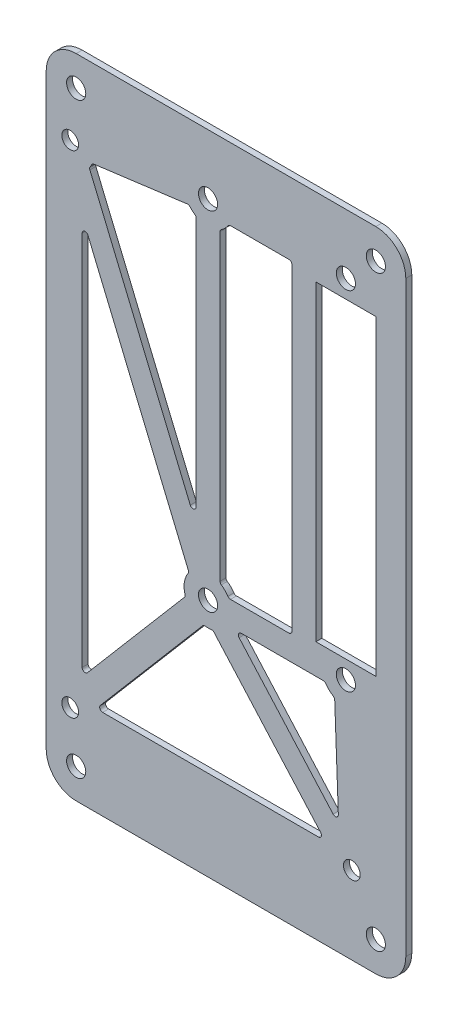
SolidWorks part; units mm, degrees
ref_plane "正面" through (0, 0, 0) normal (0, 0, 1) x (1, 0, 0)
ref_plane "平面" through (0, 0, 0) normal (0, 1, 0) x (1, 0, 0)
ref_plane "右側面" through (0, 0, 0) normal (1, 0, 0) x (0, 0, -1)
sketch "ｽｹｯﾁ1" plane through (0, 0, 0) normal (0, 0, 1) x (1, 0, 0)
  line L1 (-30, 54) -> (30, 54)
  line L2 (-30, 54) -> (-30, -54)
  line L3 (-30, -54) -> (30, -54)
  line L4 (30, 54) -> (30, -54)
  line L5 (-30, 54) -> (30, -54) construction
  line L6 (-30, -54) -> (30, 54) construction
  point P0 (0, 0)
  dimension "D1" = 108
  dimension "D2" = 60
extrude "ﾎﾞｽ - 押し出し1" add sketch "ｽｹｯﾁ1" along normal blind 1
sketch "ｽｹｯﾁ2" plane through (0, 0, 1) normal (0, 0, 1) x (1, 0, 0)
  line L0 (30, -54) -> (30, 54) construction
  line L1 (-3, 44) -> (20, 44) construction
  line L2 (-3, 44) -> (-3, -14) construction
  line L3 (-3, -14) -> (20, -14) construction
  line L4 (20, 44) -> (20, -14) construction
  line L5 (30, 54) -> (-30, 54) construction
  circle A0 centre (-3, 44) radius 1.6
  circle A1 centre (20, 44) radius 1.6
  circle A2 centre (-3, -14) radius 1.6
  circle A3 centre (20, -14) radius 1.6
  dimension "D5" = 3.2
  dimension "D6" = 3.2
  dimension "D7" = 3.2
  dimension "D8" = 3.2
  dimension "D1" = 58
  dimension "D2" = 23
  dimension "D3" = 10
  dimension "D4" = 10
extrude "ｶｯﾄ - 押し出し1" cut sketch "ｽｹｯﾁ2" against normal blind 5
sketch "ｽｹｯﾁ4" plane through (0, 0, 1) normal (0, 0, 1) x (1, 0, 0)
  line L0 (30, -54) -> (30, 54) construction
  line L1 (-25, -49) -> (25, -49) construction
  line L2 (-25, -49) -> (-25, 49) construction
  line L3 (-25, 49) -> (25, 49) construction
  line L4 (25, -49) -> (25, 49) construction
  line L5 (-25, -49) -> (25, 49) construction
  line L6 (-25, 49) -> (25, -49) construction
  line L8 (30, 54) -> (-30, 54) construction
  circle A0 centre (-25, 49) radius 1.6
  circle A1 centre (25, 49) radius 1.6
  circle A2 centre (-25, -49) radius 1.6
  circle A3 centre (25, -49) radius 1.6
  point P0 (0, 0)
  dimension "D3" = 3.2
  dimension "D4" = 3.2
  dimension "D5" = 3.2
  dimension "D6" = 3.2
  dimension "D1" = 5
  dimension "D2" = 5
extrude "ｶｯﾄ - 押し出し3" cut sketch "ｽｹｯﾁ4" against normal blind 5
fillet "ﾌｨﾚｯﾄ1" radius 5 4 edges at (30, -54, 0.5) (-30, -54, 0.5) (-30, 54, 0.5) (30, 54, 0.5)
sketch "ｽｹｯﾁ5" plane through (0, 0, 0) normal (0, 0, -1) x (-1, 0, 0)
  line L1 (-25, -11) -> (-15, -11)
  line L2 (-25, -11) -> (-25, 41)
  line L3 (-25, 41) -> (-15, 41)
  line L4 (-15, -11) -> (-15, 41)
  line L5 (-25, -11) -> (-15, 41) construction
  line L6 (-25, 41) -> (-15, -11) construction
  circle A0 centre (-20, 44) radius 1.6 construction
  circle A1 centre (-20, -14) radius 1.6 construction
  point P0 (-20, 15)
  dimension "D1" = 3
  dimension "D2" = 3
  dimension "D3" = 5
  dimension "D4" = 10
extrude "ｶｯﾄ - 押し出し4" cut sketch "ｽｹｯﾁ5" against normal through all
sketch "ｽｹｯﾁ6" plane through (0, 0, 1) normal (0, 0, 1) x (1, 0, 0)
  line L0 (-30, 49) -> (-30, -49) construction
  line L1 (25, -45) -> (-30, -45) construction
  line L2 (25, -45) -> (25, 45) construction
  line L3 (25, 45) -> (-30, 45) construction
  line L4 (-30, -45) -> (-30, 45) construction
  line L5 (30, -49) -> (30, 49) construction
  circle A0 centre (21, -41) radius 1.4
  circle A1 centre (-26, -41) radius 1.4
  circle A2 centre (-26, 41) radius 1.4
  point P6 (-30, 0)
  point P9 (30, 0)
  dimension "D4" = 4
  dimension "D5" = 4
  dimension "D6" = 2.8
  dimension "D7" = 2.8
  dimension "D8" = 4
  dimension "D10" = 4
  dimension "D11" = 4
  dimension "D12" = 2.8
  dimension "D1" = 90
  dimension "D2" = 55
  dimension "D3" = 0
  dimension "D9" = 4
extrude "ｶｯﾄ - 押し出し5" cut sketch "ｽｹｯﾁ6" against normal blind 10
sketch "ｽｹｯﾁ7" plane through (0, 0, 1) normal (0, 0, 1) x (1, 0, 0)
  line L0 (21, -41) -> (-26, -41)
  line L1 (-26, -41) -> (-3, -14)
  line L2 (21, -41) -> (-3, -14)
  line L3 (-3, -14) -> (-3, 44)
  line L4 (-3, 44) -> (-26, 41)
  line L5 (-26, 41) -> (-3, -14)
  line L6 (-26, -41) -> (-26, 41)
  line L7 (16.5463, -39) -> (-4.4948, -15.3287)
  line L8 (16.5463, -39) -> (-26, -39)
  line L9 (-24.4775, -42.2969) -> (-1.4775, -15.2969)
  line L10 (-27.5225, -39.7031) -> (-4.5225, -12.7031)
  line L11 (-24, -41) -> (-24, 41)
  line L12 (-27.8452, 40.2284) -> (-4.8452, -14.7716)
  line L13 (-24.1548, 41.7716) -> (-1.1548, -13.2284)
  line L14 (-1, -14) -> (-1, 46.2778)
  line L15 (-1, 46.2778) -> (-26.2587, 42.9832)
  line L16 (-5, -14) -> (-5, 41.7222)
  line L17 (-5, 41.7222) -> (-25.7413, 39.0168)
  line L18 (15, -11) -> (15, 41) construction
  line L19 (-3, 44) -> (11, 44)
  line L20 (-3, 44) -> (-3, -14)
  line L21 (-3, -14) -> (11, -14)
  line L22 (11, 44) -> (11, -14)
  line L23 (-3, -16) -> (11, -16)
  line L24 (-3, -12) -> (11, -12)
  line L25 (-3, 42) -> (11, 42)
  line L26 (-3, 46) -> (11, 46)
  line L27 (-3, -14) -> (20, -14)
  line L28 (20, -14) -> (21, -41)
  line L29 (18.0014, -14.074) -> (19.0014, -41.074)
  line L30 (21.9986, -13.926) -> (22.9986, -40.926)
  line L31 (-3, -16) -> (20, -16)
  line L32 (-3, -12) -> (20, -12)
  line L33 (22.4948, -39.6713) -> (-1.5052, -12.6713)
  circle A0 centre (-3, -14) radius 4
  circle A1 centre (21, -41) radius 4
  circle A2 centre (-26, -41) radius 4
  circle A3 centre (-26, 41) radius 4
  circle A4 centre (-3, 44) radius 4
  circle A5 centre (20, -14) radius 4
  dimension "D9" = 8
  dimension "D10" = 8
  dimension "D11" = 8
  dimension "D12" = 8
  dimension "D13" = 8
  dimension "D24" = 8
  dimension "D14" = 4
  dimension "D15" = 0
  dimension "D1" = 2
  dimension "D2" = 2
  dimension "D3" = 2
  dimension "D4" = 2
  dimension "D5" = 2
  dimension "D6" = 2
  dimension "D7" = 2
  dimension "D8" = 2
  dimension "D16" = 2
  dimension "D17" = 2
  dimension "D18" = 2
  dimension "D19" = 2
  dimension "D20" = 2
  dimension "D21" = 2
  dimension "D22" = 2
  dimension "D23" = 2
  dimension "D25" = 2
extrude "ｶｯﾄ - 押し出し6" cut sketch "ｽｹｯﾁ7" against normal blind 10 contours L9 L8 L7 | L12 L11 L10 | L16 L17 L13 | A4 L14 A0 L24 L22 L25 | A5 L31 L33 L29 region at (-2.6964, -31.7072, 1) region at (-17.8374, -6.0159, 1) region at (12.7321, -22.5553, 1) region at (-11.0484, 25.6402, 1) region at (5.0214, 15, 1)
fillet "ﾌｨﾚｯﾄ3" radius 0.5 23 edges at (-1, -10.5359, 0.5) (0.4641, -12, 0.5) (11, -12, 0.5) (11, 42, 0.5) (-1, 40.5359, 0.5) (0.4641, 42, 0.5) (-5, 40.5359, 0.5) (-6.1763, 41.5688, 0.5) (-5, -4.0334, 0.5) (-22.8184, 38.5757, 0.5) (-22.3063, 39.4648, 0.5) (-24, 31.0334, 0.5) (-6.1816, -11.5757, 0.5) (-6.7688, -15.3401, 0.5) (-24, -35.568, 0.5) (-21.669, -39, 0.5) (16.5463, -39, 0.5) (-3.7239, -17.934, 0.5) (-2.1934, -17.9178, 0.5) (1.4537, -16, 0.5) (18.7953, -35.5093, 0.5) (16.5359, -16, 0.5) (18.1296, -17.5358, 0.5)
